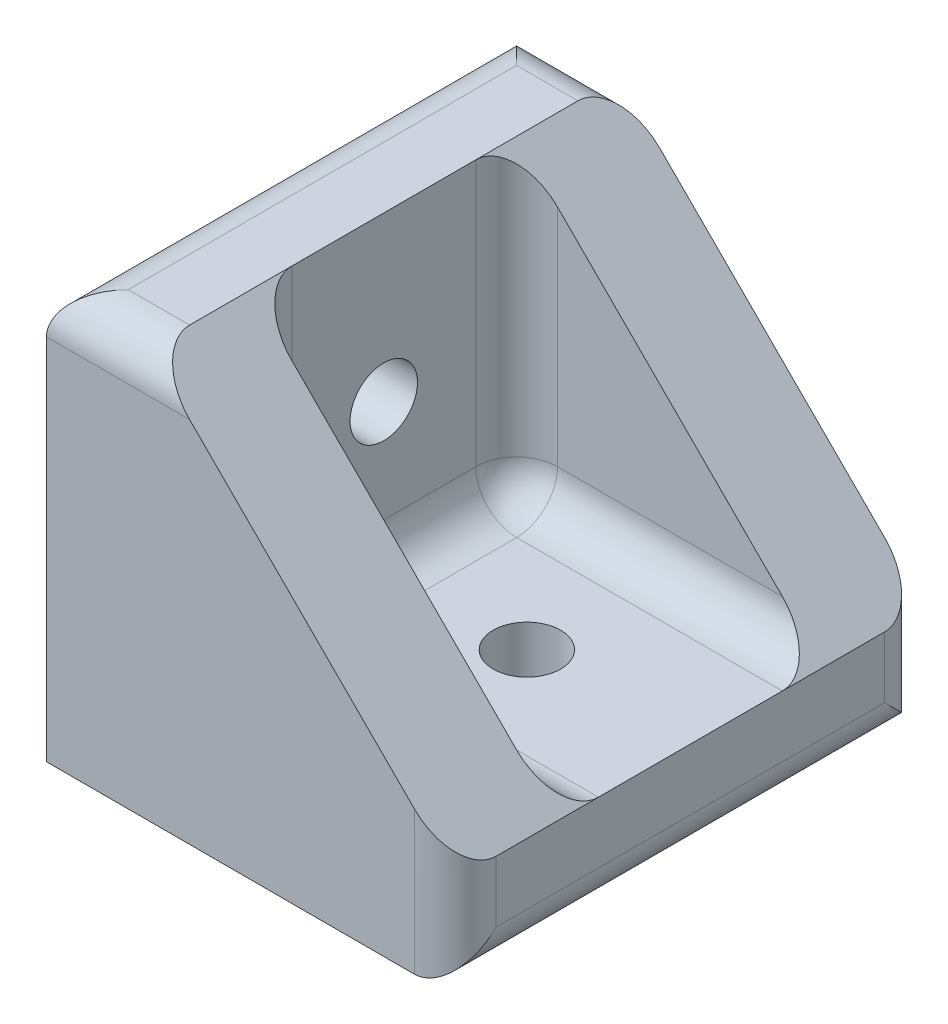
SolidWorks part; units mm, degrees
ref_plane "Front Plane" through (0, 0, 0) normal (0, 0, 1) x (1, 0, 0)
ref_plane "Top Plane" through (0, 0, 0) normal (0, 1, 0) x (1, 0, 0)
ref_plane "Right Plane" through (0, 0, 0) normal (1, 0, 0) x (0, 0, -1)
sketch "Sketch1" plane through (0, 0, 0) normal (0, 0, 1) x (1, 0, 0)
  line L0 (0, 0) -> (0, 20)
  line L1 (0, -55) -> (0, 55) construction
  line L2 (0, 20) -> (5, 20)
  line L5 (20, 5) -> (20, 0)
  line L6 (55, 0) -> (-55, 0) construction
  line L7 (20, 0) -> (0, 0)
  line L8 (5, 20) -> (20, 5)
  dimension "D1" = 5
  dimension "D2" = 5
  dimension "D3" = 20
  dimension "D4" = 20
extrude "Boss-Extrude2" add sketch "Sketch1" against normal blind 23
shell "Shell1" thickness 5 removed face at (12.5, 12.5, -11.5) removed face at (2.5, 20, -11.5) removed face at (20, 2.5, -11.5)
sketch "Sketch2" plane through (0, 5, 0) normal (0, 1, 0) x (1, 0, 0)
  line L0 (20, 11.5) -> (-3.555, 11.5) construction
  line L1 (20, 18) -> (20, 5) construction
  line L2 (0, -55) -> (0, 55) construction
  point P4 (12, 11.5)
  dimension "D1" = 12
sketch "Sketch3" plane through (5, 0, 0) normal (1, 0, 0) x (0, 0, -1)
  line L0 (11.5, 20) -> (11.5, -1.8484) construction
  line L1 (18, 20) -> (5, 20) construction
  line L2 (55, 0) -> (-55, 0) construction
  point P5 (11.5, 12)
  dimension "D1" = 12
fillet "Fillet1" radius 2 5 edges at (5, 5, -11.5) (5, 12.5, -18) (12.5, 5, -18) (5, 12.5, -5) (12.5, 5, -5)
fillet "Fillet3" radius 2 6 edges at (2.5, 20, -23) (20, 2.5, -23) (20, 2.5, 0) (2.5, 20, 0) (20, 0, -11.5) (0, 20, -11.5)
hole_wizard "Tap Drill for M4x0.7 Tap1" positions "3DSketch1" profile "Sketch6" hole size "M4x0.7" standard "ANSI Metric" end condition through all
sketch3d "3DSketch1"
  point P0 (5, 12, -11.5)
  point P3 (12, 5, -11.5)
sketch "Sketch6" plane through (5, 12, -11.5) normal (0, 1, 0) x (0, 0, -1)
  line L0 (0, 0) -> (0, 5)
  line L1 (0, 5) -> (1.65, 5)
  line L2 (1.65, 5) -> (1.65, 0)
  line L5 (1.65, 0) -> (0, 0)
  line L11 (0, -6.35) -> (0, 107.95) construction
  dimension "Thru Hole Dia." = 3.3
  dimension "Thru Hole Depth" = 5
